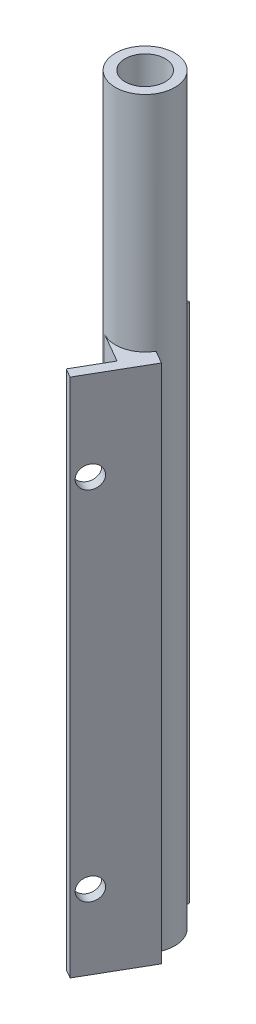
SolidWorks part; units mm, degrees
ref_plane "Front Plane" through (0, 0, 0) normal (0, 0, 1) x (1, 0, 0)
ref_plane "Top Plane" through (0, 0, 0) normal (0, 1, 0) x (1, 0, 0)
ref_plane "Right Plane" through (0, 0, 0) normal (1, 0, 0) x (0, 0, -1)
sketch "Sketch1" plane through (0, 0, 0) normal (0, 1, 0) x (1, 0, 0)
  circle A0 centre (0, 0) radius 5.08
  dimension "D1" = 10.16
extrude "Boss-Extrude1" add sketch "Sketch1" along normal blind 127
sketch "Sketch2" plane through (0, 0, 0) normal (0, -1, 0) x (1, 0, 0)
  circle A0 centre (0, 0) radius 3.429
  dimension "D1" = 6.858
extrude "Cut-Extrude1" cut sketch "Sketch2" against normal through all
sketch "Sketch3" plane through (0, 0, 0) normal (0, -1, 0) x (1, 0, 0)
  line L0 (0, 0) -> (0, -5.08) construction
  line L1 (0, -5.08) -> (-5.08, -5.08) construction
  line L2 (0, 0) -> (-2.54, 4.3994) construction
  line L3 (0, 0) -> (-5.08, 0) construction
  line L4 (-2.54, 4.3994) -> (1.8594, 6.9394) construction
  line L5 (8.7988, -5.08) -> (-1.3156, 12.4387) construction
  line L7 (0, -5.08) -> (-11.43, -5.08) construction
  line L8 (-1.3156, 12.4387) -> (-5.715, 9.8987)
  line L9 (-11.43, -5.08) -> (-11.43, 0)
  line L10 (-5.715, 9.8987) -> (-2.54, 4.3994)
  line L11 (-11.43, 0) -> (-5.08, 0)
  line L13 (-11.43, -5.08) -> (-11.43, -10.16)
  line L14 (-11.43, -10.16) -> (0, -10.16)
  line L15 (0, -10.16) -> (0, -5.08)
  line L17 (4.3994, 2.54) -> (8.7988, 5.08)
  line L18 (8.7988, 5.08) -> (3.0838, 14.9787)
  line L19 (3.0838, 14.9787) -> (-1.3156, 12.4387)
  arc A0 (-5.08, 0) -> (-2.54, 4.3994) centre (-0.7771, 0.4486) ccw
  circle A1 centre (0, 0) radius 3.429 construction
  circle A2 centre (0, 0) radius 5.08 construction
  arc A3 (4.3994, 2.54) -> (0, -5.08) centre (0, 0) cw
  point P9 (0, -5.08)
  dimension "D1" = 60
  dimension "D2" = 6.35
  dimension "D3" = 6.35
  dimension "D4" = 5.08
  dimension "D5" = 5.08
extrude "Boss-Extrude2" add sketch "Sketch3" against normal blind 88.9
sketch "Sketch4" plane through (0, 0, 0) normal (0, 0, 1) x (1, 0, 0)
  line L1 (-5.08, 88.9) -> (-5.08, 0) construction
  line L2 (-5.08, 88.9) -> (-11.43, 88.9) construction
  circle A0 centre (-8.89, 81.28) radius 1.905
  circle A1 centre (-8.89, 20.32) radius 1.905
  dimension "D3" = 3.81
  dimension "D1" = 7.62
  dimension "D2" = 68.58
  dimension "D4" = 3.81
extrude "Hole Cuts 1" cut sketch "Sketch4" against normal up to next
sketch "Sketch7" plane through (0, 0, 0) normal (0.866, 0, 0.5) x (0.5, 0, -0.866)
  line L1 (-5.08, 88.9) -> (-5.08, 0) construction
  line L3 (-2.54, 88.9) -> (-5.715, 88.9) construction
  line L5 (0, 88.9) -> (-11.43, 88.9) construction
  circle A0 centre (-8.89, 73.66) radius 1.905
  circle A1 centre (-8.89, 12.7) radius 1.905
  dimension "D2" = 3.81
  dimension "D1" = 3.81
  dimension "D3" = 15.24
  dimension "D4" = 76.2
extrude "Hole Cuts 2" cut sketch "Sketch7" along normal up to next
sketch "Sketch8" plane through (0, 0, 0) normal (0, -1, 0) x (1, 0, 0)
  line L0 (-5.715, 9.8987) -> (-1.7555, 12.1847)
  line L1 (3.0838, 14.9787) -> (-5.715, 9.8987) construction
  line L2 (-11.43, 0) -> (-11.43, -4.572)
  line L3 (-11.43, 0) -> (-11.43, -10.16) construction
  line L4 (-5.715, 9.8987) -> (-2.54, 4.3994)
  line L5 (-11.43, 0) -> (-5.08, 0)
  line L6 (-1.7555, 12.1847) -> (1.4195, 6.6854)
  line L7 (1.4195, 6.6854) -> (-2.54, 4.3994)
  line L8 (-11.43, -4.572) -> (-5.08, -4.572)
  line L9 (-5.08, -4.572) -> (-5.08, 0)
  dimension "D1" = 4.572
extrude "Cut-Extrude7" cut sketch "Sketch8" against normal up to next
sketch "Sketch9" plane through (0, 0, -10.16) normal (0, 0, -1) x (-1, 0, 0)
  line L1 (11.43, 88.9) -> (0, 88.9)
  line L2 (11.43, 88.9) -> (11.43, 0)
  line L3 (11.43, 0) -> (0, 0)
  line L4 (0, 88.9) -> (0, 0)
extrude "Cut-Extrude8" cut sketch "Sketch9" against normal blind 2.54
sketch "Sketch10" plane through (8.7988, 0, 5.08) normal (0.866, 0, 0.5) x (0.5, 0, -0.866)
  line L1 (-11.43, 0) -> (0, 0)
  line L2 (-11.43, 0) -> (-11.43, 88.9)
  line L3 (-11.43, 88.9) -> (0, 88.9)
  line L4 (0, 0) -> (0, 88.9)
extrude "Cut-Extrude9" cut sketch "Sketch10" against normal blind 2.54
sketch "Sketch11" plane through (0, 0, -4.572) normal (0, 0, 1) x (1, 0, 0)
  line L1 (-11.43, 88.9) -> (-5.08, 88.9)
  line L2 (-11.43, 88.9) -> (-11.43, 0)
  line L3 (-11.43, 0) -> (-5.08, 0)
  line L4 (-5.08, 88.9) -> (-5.08, 0)
extrude "Cut-Extrude10" cut sketch "Sketch11" against normal blind 1.27
sketch "Sketch13" plane through (3.9595, 0, 2.286) normal (-0.866, 0, -0.5) x (-0.5, 0, 0.866)
  line L1 (5.08, 0) -> (11.43, 0)
  line L2 (5.08, 0) -> (5.08, 88.9)
  line L3 (5.08, 88.9) -> (11.43, 88.9)
  line L4 (11.43, 0) -> (11.43, 88.9)
extrude "Cut-Extrude11" cut sketch "Sketch13" against normal blind 1.27
